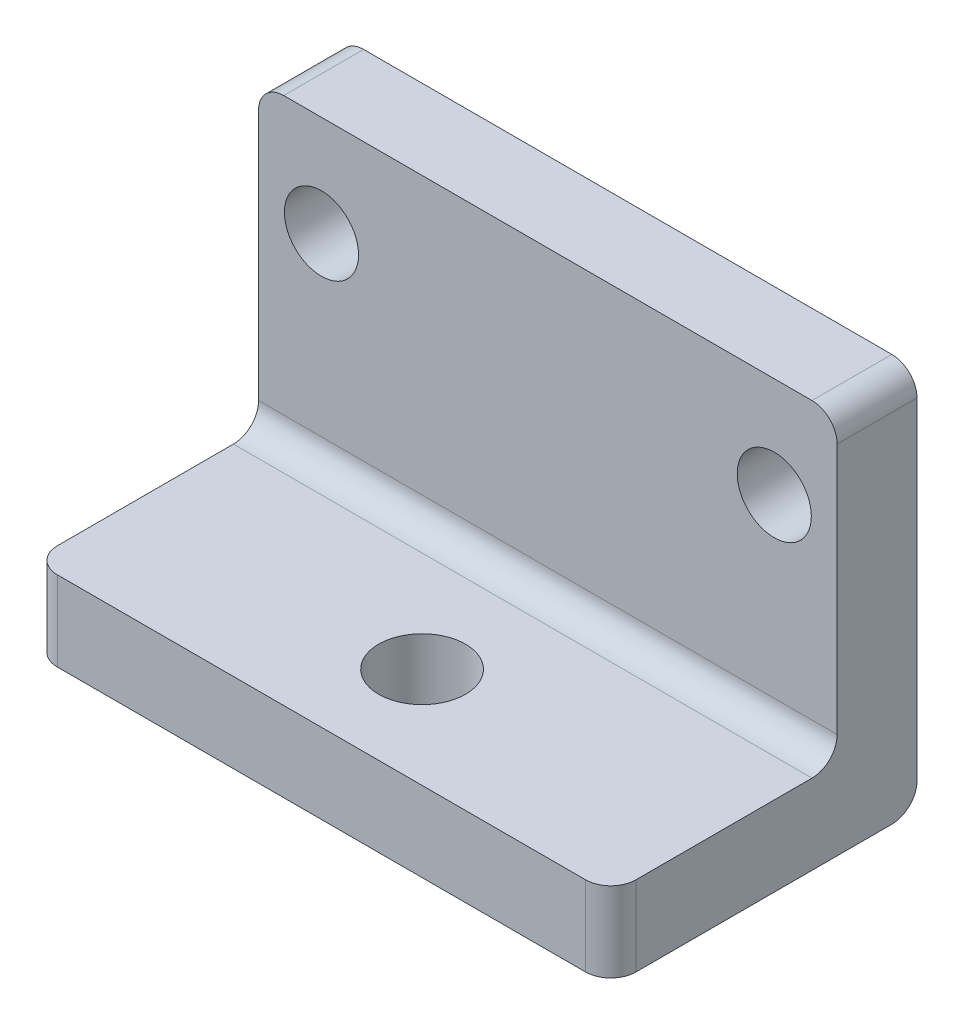
SolidWorks part; units mm, degrees
ref_plane "Front Plane" through (0, 0, 0) normal (0, 0, 1) x (1, 0, 0)
ref_plane "Top Plane" through (0, 0, 0) normal (0, 1, 0) x (1, 0, 0)
ref_plane "Right Plane" through (0, 0, 0) normal (1, 0, 0) x (0, 0, -1)
sketch "Sketch1" plane through (0, 0, 0) normal (0, 0, 1) x (1, 0, 0)
  line L0 (0, -10) -> (23, -10)
  line L1 (0, 0) -> (23, 0)
  line L2 (0, 0) -> (0, -13.175)
  line L3 (0, -13.175) -> (23, -13.175)
  line L4 (23, 0) -> (23, -13.175)
  line L5 (0, 0) -> (0, 2)
  line L6 (0, 2) -> (23, 2)
  line L7 (23, 2) -> (23, 0)
  circle A0 centre (2.5, -2) radius 1.4732
  circle A1 centre (20.5, -2) radius 1.4732
  dimension "D2" = 2.9464
  dimension "D1" = 18
  dimension "D4" = 3.175
  dimension "D5" = 23
  dimension "D6" = 2.5
  dimension "D7" = 2
  dimension "D3" = 10
  dimension "D8" = 2
extrude "Boss-Extrude1" add sketch "Sketch1" along normal blind 3.175 contours L4 L1 L2 L0 A1 A0 | L4 L0 L2 L3 | L7 L6 L5 L1 region at (11.5, -5.1891, 0) region at (11.5, -11.5875, 0) region at (11.5, 1, 0)
extrude "Boss-Extrude2" add sketch "Sketch1<3>" along normal blind 9 from surface contours L4 L0 L2 L3 region at (11.5, -11.5875, 0) starting at face at (21.9732, -2, 3.175)
sketch "Sketch1<3>" plane through (0, 0, 0) normal (0, 0, 1) x (1, 0, 0) same geometry as "Sketch1"
sketch "Mount Hole Location" plane through (0, -10, 0) normal (0, 1, 0) x (1, 0, 0)
  line L0 (0, -12.175) -> (23, -12.175) construction
  point P0 (11.5, -8.175)
  point P4 (11.5, -12.175)
  dimension "D1" = 4
hole_wizard "#8-32 Tapped Hole1" positions "3DSketch1" profile "Sketch3" tap size "#8-32" standard "ANSI Inch" end condition through all
sketch3d "3DSketch1"
  point P0 (11.5, -10, 8.175)
sketch "Sketch3" plane through (11.5, -10, 8.175) normal (1, 0, 0) x (0, 0, 1)
  line L0 (0, 0) -> (0, 3.175)
  line L1 (0, 3.175) -> (1.7272, 3.175)
  line L2 (1.7272, 3.175) -> (1.7272, 0)
  line L5 (1.7272, 0) -> (0, 0)
  line L11 (0, -6.35) -> (0, 107.95) construction
  dimension "Thru Tap Drill Dia." = 3.4544
  dimension "Thru Tap Drill Depth" = 3.175
cosmetic thread "Hole Thread1" parameters "D2"=4.1656
fillet "Fillet1" radius 1 6 edges at (0, -11.5875, 12.175) (23, -11.5875, 12.175) (11.5, -13.175, 0) (11.5, -10, 3.175) (23, 2, 1.5875) (0, 2, 1.5875)
equation "\"D6@Sketch1\"=(\"D5@Sketch1\"-\"D1@Sketch1\")/2"
